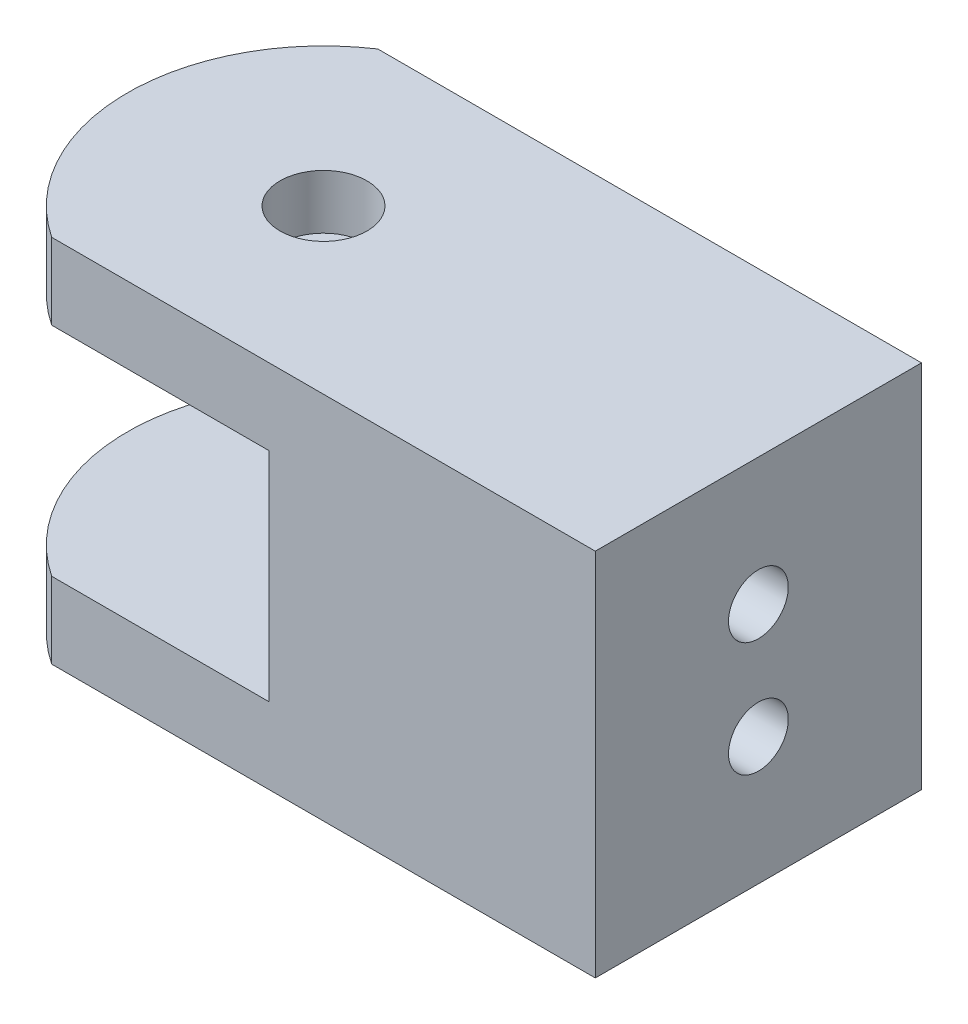
SolidWorks part; units mm, degrees
ref_plane "Plan de face" through (0, 0, 0) normal (0, 0, 1) x (1, 0, 0)
ref_plane "Plan de dessus" through (0, 0, 0) normal (0, 1, 0) x (1, 0, 0)
ref_plane "Plan de droite" through (0, 0, 0) normal (1, 0, 0) x (0, 0, -1)
sketch "Esquisse1" plane through (0, 0, 0) normal (0, 0, 1) x (1, 0, 0)
  line L1 (0, 0) -> (50, 0)
  line L2 (0, 0) -> (0, 34)
  line L3 (0, 34) -> (50, 34)
  line L4 (50, 0) -> (50, 34)
  dimension "D1" = 34
  dimension "D2" = 50
extrude "Boss.-Extru.1" add sketch "Esquisse1" along normal blind 30
sketch "Esquisse3" plane through (0, 34, 0) normal (0, 1, 0) x (1, 0, 0)
  line L0 (0, 0) -> (20, -30) construction
  line L1 (50, -30) -> (0, -30) construction
  line L2 (20, -30) -> (0, -30) construction
  line L7 (50, 0) -> (0, 0)
  line L8 (0, 0) -> (0, -30)
  line L9 (0, -30) -> (50, -30)
  line L10 (50, -30) -> (50, 0)
  line L12 (0, 0) -> (0, -30)
  arc A0 (0, 0) -> (0, -30) centre (10, -15) ccw
  point P3 (10, -15)
  dimension "D1" = 20
extrude "Boss.-Extru.2" add sketch "Esquisse3" against normal blind 7
ref_plane "Plan1" through (0, 17, 0) normal (0, 1, 0) x (1, 0, 0)
mirror "Symétrie1" about plane through (0, 17, 0) normal (0, 1, 0) of "Boss.-Extru.2"
sketch "Esquisse4" plane through (0, 34, 0) normal (0, 1, 0) x (1, 0, 0)
  line L0 (0, 0) -> (20, -30) construction
  line L1 (50, -30) -> (0, -30) construction
  line L2 (20, -30) -> (0, -30) construction
  circle A0 centre (10, -15) radius 4
  dimension "D1" = 20
  dimension "D2" = 8
extrude "Enlèv. mat.-Extru.1" cut sketch "Esquisse4" against normal blind 5
sketch "Esquisse5" plane through (0, 29, 0) normal (0, 1, 0) x (1, 0, 0)
  circle A0 centre (10, -15) radius 2.75
  dimension "D1" = 5.5
extrude "Enlèv. mat.-Extru.2" cut sketch "Esquisse5" against normal through all
sketch "Esquisse6" plane through (0, 0, 0) normal (0, -1, 0) x (1, 0, 0)
  line L0 (0, 0) -> (50, 0) construction
  line L1 (7.1132, 20) -> (4.2265, 15)
  line L2 (4.2265, 15) -> (7.1132, 10)
  line L3 (7.1132, 10) -> (12.8868, 10)
  line L4 (12.8868, 10) -> (15.7735, 15)
  line L5 (15.7735, 15) -> (12.8868, 20)
  line L6 (12.8868, 20) -> (7.1132, 20)
  circle A0 centre (10, 15) radius 5 construction
  dimension "D1" = 10
extrude "Enlèv. mat.-Extru.3" cut sketch "Esquisse6" against normal blind 5
sketch "Esquisse7" plane through (0, 0, 0) normal (-1, 0, 0) x (0, 0, 1)
  line L0 (15, 7) -> (15, 11.7267) construction
  line L3 (30, 7) -> (0, 7) construction
  line L4 (15, 11.7267) -> (15, 22.2733) construction
  line L5 (15, 22.2733) -> (15, 27) construction
  line L6 (30, 27) -> (0, 27) construction
  circle A0 centre (15, 11.7267) radius 2.75
  circle A1 centre (15, 22.2733) radius 2.75
  dimension "D1" = 5.5
extrude "Enlèv. mat.-Extru.4" cut sketch "Esquisse7" against normal through all
sketch "Esquisse8" plane through (0, 0, 0) normal (-1, 0, 0) x (0, 0, 1)
  circle A0 centre (15, 11.7267) radius 4
  circle A1 centre (15, 22.2733) radius 4
  dimension "D1" = 8
extrude "Enlèv. mat.-Extru.5" cut sketch "Esquisse8" against normal blind 45
sketch "Esquisse9" plane through (0, 0, 0) normal (0, 0, -1) x (-1, 0, 0)
  line L1 (0, 7) -> (-20, 7)
  line L2 (0, 7) -> (0, 27)
  line L3 (0, 27) -> (-20, 27)
  line L4 (-20, 7) -> (-20, 27)
  dimension "D1" = 20
extrude "Enlèv. mat.-Extru.6" cut sketch "Esquisse9" against normal through all
sketch "Esquisse11" plane through (0, 7, 0) normal (0, 1, 0) x (1, 0, 0)
  circle A0 centre (10, -15) radius 18.0278
extrude "Enlèv. mat.-Extru.7" cut sketch "Esquisse11" along normal up to surface (20 mm away) up to face at (7.9931, 27, 15)
